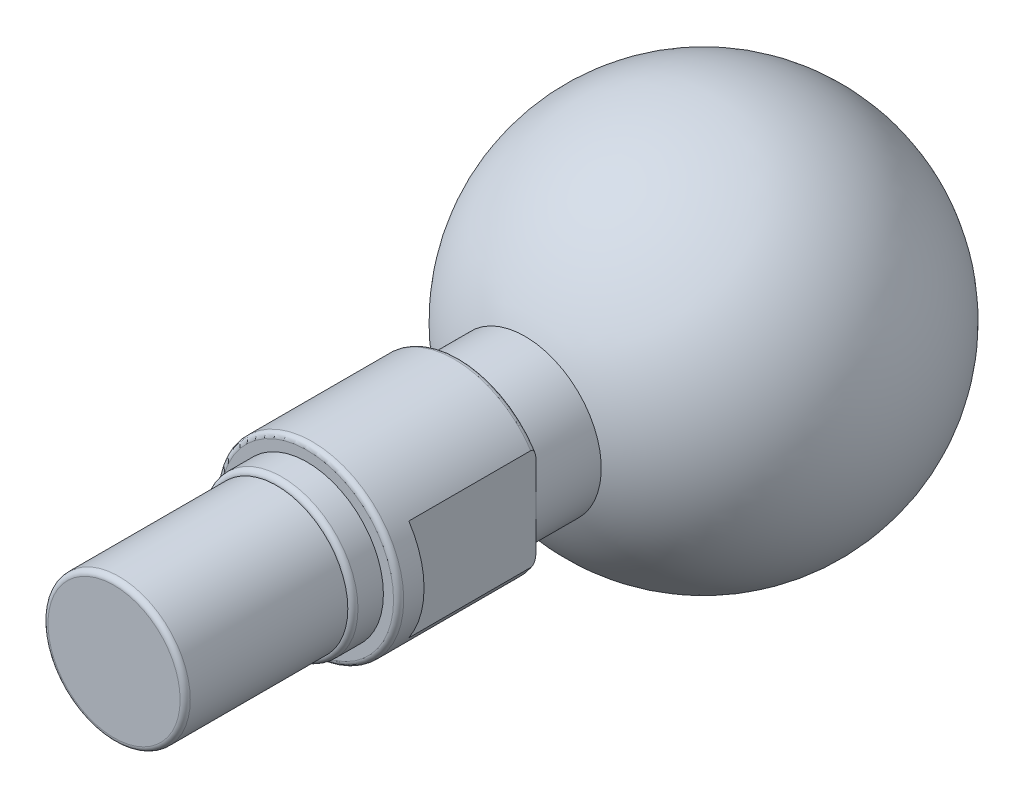
SolidWorks part; units mm, degrees
ref_plane "前视基准面" through (0, 0, 0) normal (0, 0, 1) x (1, 0, 0)
ref_plane "上视基准面" through (0, 0, 0) normal (0, 1, 0) x (1, 0, 0)
ref_plane "右视基准面" through (0, 0, 0) normal (1, 0, 0) x (0, 0, -1)
sketch "草图1" plane through (0, 0, 0) normal (0, 0, 1) x (1, 0, 0)
  circle A0 centre (0, 0) radius 18
extrude "凸台-拉伸1" add sketch "草图1" along normal blind 116
sketch "草图2" plane through (0, 0, 116) normal (0, 0, 1) x (1, 0, 0)
  circle A0 centre (0, 0) radius 18
  circle A1 centre (0, 0) radius 15
extrude "切除-拉伸1" cut sketch "草图2" against normal blind 38
sketch "草图3" plane through (0, 0, 116) normal (0, 0, 1) x (1, 0, 0)
  circle A0 centre (0, 0) radius 15
  circle A1 centre (0, 0) radius 14
extrude "切除-拉伸2" cut sketch "草图3" against normal blind 32
cosmetic thread "装饰螺纹线4" parameters "D2"=23.752
sketch "草图4" plane through (0, 0, 0) normal (0, 0, -1) x (-1, 0, 0)
  circle A0 centre (0, 0) radius 15
  circle A1 centre (0, 0) radius 18
extrude "切除-拉伸3" cut sketch "草图4" against normal blind 48
sketch "草图5" plane through (0, 0, 0) normal (0, 0, -1) x (-1, 0, 0)
  line L2 (0, 28) -> (0, -28)
  line L3 (0, 38.2) -> (0, 28)
  line L4 (0, -28) -> (0, -38.2)
  arc A3 (0, -38.2) -> (0, 38.2) centre (0, 0) ccw
revolve "旋转2" add sketch "草图5" angle 360 about L2 region at (-18.0076, 0, 0)
sketch "草图6" plane through (0, 0, 48) normal (0, 0, -1) x (-1, 0, 0)
  line L1 (15, 0) -> (15, 35.8689)
  line L2 (15, 35.8689) -> (38.2658, 35.8689)
  line L3 (38.2658, 35.8689) -> (38.2658, -37.8689)
  line L4 (38.2658, -37.8689) -> (15, -37.8689)
  line L5 (15, -37.8689) -> (15, 0)
  line L7 (-15, -37.8689) -> (-15, 0)
  line L8 (-38.2658, -37.8689) -> (-15, -37.8689)
  line L9 (-38.2658, 35.8689) -> (-38.2658, -37.8689)
  line L10 (-15, 35.8689) -> (-38.2658, 35.8689)
  line L11 (-15, 0) -> (-15, 35.8689)
  dimension "D1" = 15
  dimension "D2" = 15
extrude "切除-拉伸4" cut sketch "草图6" against normal blind 25
fillet "圆角1" radius 1 4 edges at (15, 0, 84) (0, 18, 48) (18, 0, 78) (14, 0, 116)
fillet "圆角2" radius 1 1 edges at (0, -18, 48)
